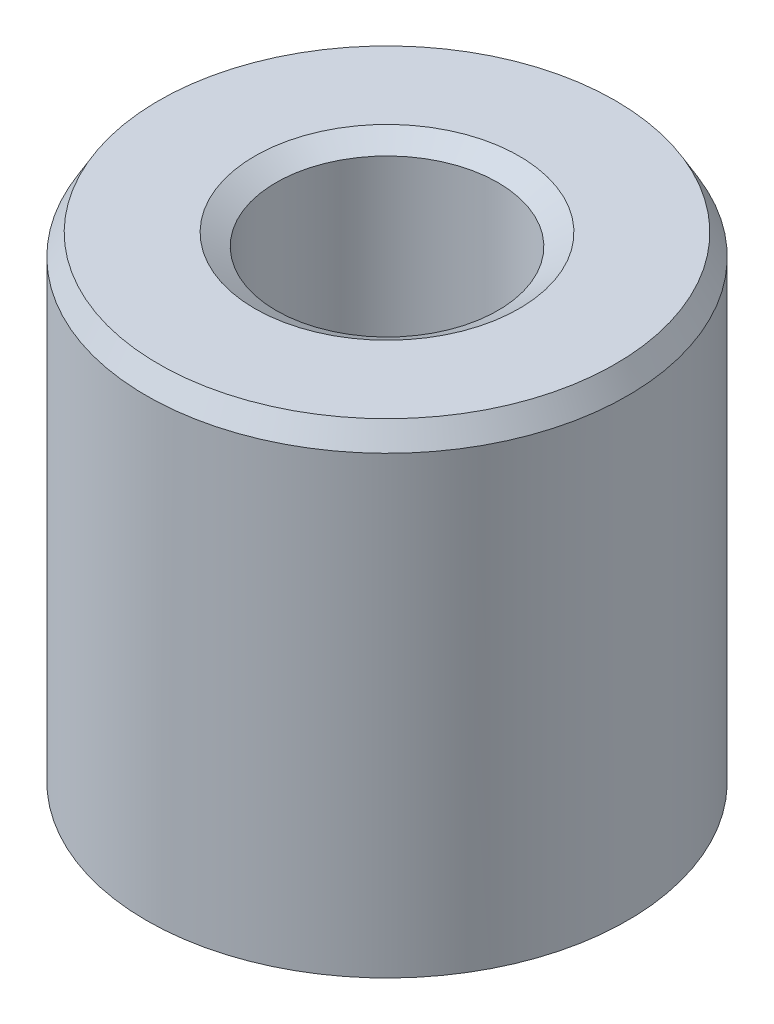
SolidWorks part; units mm, degrees
ref_plane "Front Plane" through (0, 0, 0) normal (0, 0, 1) x (1, 0, 0)
ref_plane "Top Plane" through (0, 0, 0) normal (0, 1, 0) x (1, 0, 0)
ref_plane "Right Plane" through (0, 0, 0) normal (1, 0, 0) x (0, 0, -1)
sketch "Sketch1" plane through (0, 0, 0) normal (0, 1, 0) x (1, 0, 0)
  circle A0 centre (0, 0) radius 17.5
  dimension "SLEEVE_OD" = 35
extrude "Boss-Extrude1" add sketch "Sketch1" along normal blind 35.4955
sketch "Sketch2" plane through (0, 0, 0) normal (0, 1, 0) x (1, 0, 0)
  circle A0 centre (0, 0) radius 8.0675
  dimension "BORE_D" = 16.135
extrude "Cut-Extrude1" cut sketch "Sketch2" along normal through all
chamfer "Chamfer1" distance 1.5477 angle 30 4 edges at (0, 35.4955, 8.0675) (0, 0, 8.0675) (0, 0, 17.5) (0, 35.4955, 17.5) first distance on face at (0, 35.4955, 8.0675) first distance on face at (0, 0, 8.0675) first distance on face at (0, 35.4955, 17.5)
